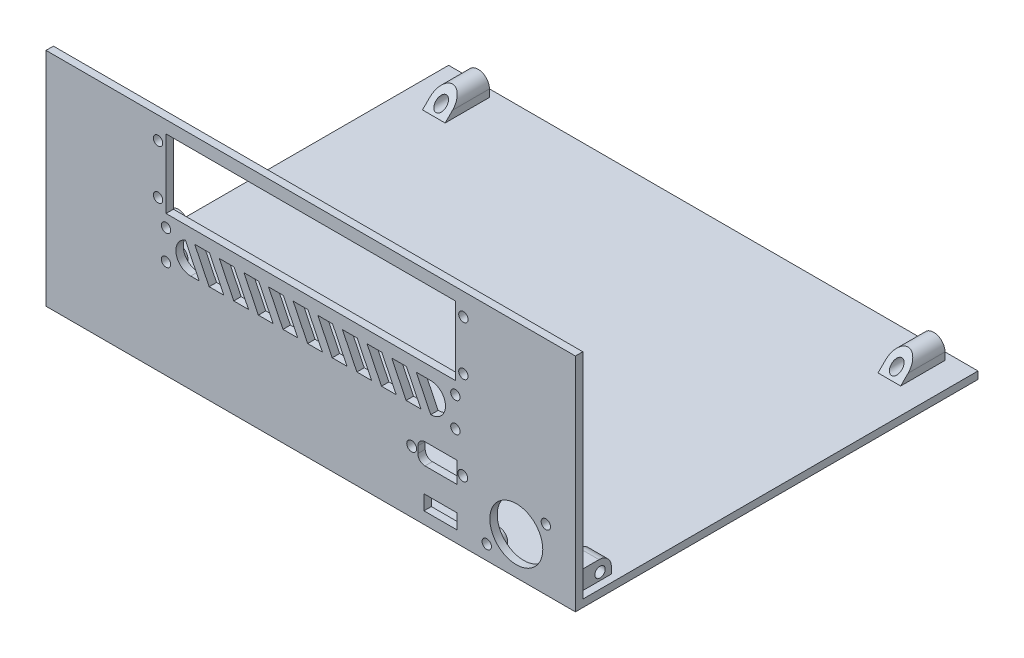
SolidWorks part; units mm, degrees
ref_plane "Płaszczyzna przednia" through (0, 0, 0) normal (0, 0, 1) x (1, 0, 0)
ref_plane "Płaszczyzna górna" through (0, 0, 0) normal (0, 1, 0) x (1, 0, 0)
ref_plane "Płaszczyzna prawa" through (0, 0, 0) normal (1, 0, 0) x (0, 0, -1)
sketch "Szkic1" plane through (0, 0, 0) normal (0, 0, 1) x (1, 0, 0)
  line L1 (0, 0) -> (215, 0)
  line L2 (0, 0) -> (0, 90)
  line L3 (0, 90) -> (215, 90)
  line L4 (215, 0) -> (215, 90)
  dimension "D1" = 215
  dimension "D2" = 90
extrude "Dodanie-wyciągnięcie1" add sketch "Szkic1" along normal blind 3
ref_plane "Płaszczyzna1" through (107.5, 0, 0) normal (1, 0, 0) x (0, 0, -1)
sketch "Szkic5" plane through (0, 0, 3) normal (0, 0, 1) x (1, 0, 0)
  line L0 (215, 90) -> (0, 90) construction
  line L1 (48.75, 85) -> (166.25, 85)
  line L2 (48.75, 85) -> (48.75, 57)
  line L3 (48.75, 57) -> (166.25, 57)
  line L4 (166.25, 85) -> (166.25, 57)
  line L5 (107.5, 90) -> (107.5, 105.9064) construction
  line L6 (48.75, 71) -> (107.5, 71) construction
  circle A0 centre (45.5, 81) radius 1.9
  circle A2 centre (45.5, 61) radius 1.9
  circle A3 centre (169.5, 61) radius 1.9
  circle A4 centre (169.5, 81) radius 1.9
  point P6 (107.5, 85)
  dimension "D6" = 3.8
  dimension "D4" = 20
  dimension "D1" = 5
  dimension "D2" = 28
  dimension "D3" = 117.5
  dimension "D5" = 62
extrude "Wytnij-wyciągnięcie2" cut sketch "Szkic5" against normal blind 35 contours A0 | A2 | A3 | A4 | L2 L3 L4 L1 region at (45.5, 81, 3) region at (45.5, 61, 3) region at (169.5, 61, 3) region at (169.5, 81, 3)
sketch "Szkic6" plane through (0, 0, 3) normal (0, 0, 1) x (1, 0, 0)
  line L1 (153.5, 10.8) -> (167, 10.8)
  line L2 (153.5, 10.8) -> (153.5, 4.8)
  line L3 (153.5, 4.8) -> (167, 4.8)
  line L4 (167, 10.8) -> (167, 4.8)
  line L10 (215, 0) -> (215, 90) construction
  line L11 (0, 0) -> (215, 0) construction
  line L13 (167, 20.8) -> (153.9, 20.8)
  line L14 (167, 20.8) -> (167, 29.3)
  line L15 (167, 29.3) -> (153.9, 29.3)
  line L16 (151, 23.7) -> (151, 26.4)
  circle A0 centre (191, 15.35) radius 10.75
  circle A1 centre (203, 24.85) radius 1.9
  circle A2 centre (179, 5.85) radius 1.9
  arc A3 (153.9, 20.8) -> (151, 23.7) centre (153.9, 23.7) cw
  arc A4 (153.9, 29.3) -> (151, 26.4) centre (153.9, 26.4) ccw
  circle A5 centre (148.5, 25.05) radius 2
  circle A6 centre (169.25, 25.05) radius 2
  point P16 (151, 20.8)
  dimension "D9" = 3.8
  dimension "D10" = 3.8
  dimension "D15" = 21.5
  dimension "D16" = 2.9
  dimension "D21" = 4
  dimension "D22" = 4
  dimension "D3" = 8.5
  dimension "D4" = 16
  dimension "D1" = 48
  dimension "D2" = 13.5
  dimension "D5" = 6
  dimension "D6" = 4.8
  dimension "D7" = 24
  dimension "D8" = 15.35
  dimension "D11" = 12
  dimension "D12" = 9.5
  dimension "D13" = 12
  dimension "D14" = 9.5
  dimension "D17" = 24
  dimension "D18" = 10
  dimension "D19" = 2.5
  dimension "D20" = 2.25
extrude "Wytnij-wyciągnięcie3" cut sketch "Szkic6" against normal through all
sketch "Szkic8" plane through (0, 0, 0) normal (0, 0, -1) x (-1, 0, 0)
  circle A0 centre (-179, 5.85) radius 3.5
  circle A1 centre (-203, 24.85) radius 3.5
  circle A2 centre (-203, 24.85) radius 2
  circle A3 centre (-179, 5.85) radius 2
  dimension "D1" = 7
  dimension "D2" = 7
  dimension "D3" = 4
  dimension "D4" = 4
extrude "Dodanie-wyciągnięcie4" add sketch "Szkic8" along normal blind 2
sketch "Szkic9" plane through (0, 0, 0) normal (0, 0, -1) x (-1, 0, 0)
  line L0 (-156.25, 46) -> (-58.75, 46) construction
  line L1 (-156.25, 52) -> (-58.75, 52)
  line L2 (-156.25, 40) -> (-58.75, 40)
  line L3 (-166.25, 57) -> (-48.75, 57) construction
  line L4 (-166.25, 57) -> (-166.25, 85) construction
  line L5 (-48.75, 57) -> (-48.75, 85) construction
  line L6 (-156.25, 40) -> (-150.385, 52)
  line L7 (-152.25, 40) -> (-146.385, 52)
  line L8 (-146.25, 40) -> (-140.385, 52)
  line L9 (-142.25, 40) -> (-136.385, 52)
  line L10 (-136.25, 40) -> (-130.385, 52)
  line L11 (-132.25, 40) -> (-126.385, 52)
  line L12 (-126.25, 40) -> (-120.385, 52)
  line L13 (-122.25, 40) -> (-116.385, 52)
  line L14 (-116.25, 40) -> (-110.385, 52)
  line L15 (-112.25, 40) -> (-106.385, 52)
  line L16 (-106.25, 40) -> (-100.385, 52)
  line L17 (-102.25, 40) -> (-96.385, 52)
  line L18 (-96.25, 40) -> (-90.385, 52)
  line L19 (-92.25, 40) -> (-86.385, 52)
  line L20 (-86.25, 40) -> (-80.385, 52)
  line L21 (-82.25, 40) -> (-76.385, 52)
  line L22 (-76.25, 40) -> (-70.385, 52)
  line L23 (-72.25, 40) -> (-66.385, 52)
  line L24 (-66.25, 40) -> (-60.385, 52)
  line L25 (-62.25, 40) -> (-56.583, 51.595)
  line L26 (-107.5, -6.1587) -> (-107.5, 71.4956) construction
  line L29 (-107.5, 46) -> (-179.9248, 46) construction
  arc A0 (-156.25, 52) -> (-156.25, 40) centre (-156.25, 46) ccw
  arc A1 (-58.75, 40) -> (-58.75, 52) centre (-58.75, 46) ccw
  circle A2 centre (-166.25, 52) radius 1.9
  circle A3 centre (-166.25, 40) radius 1.9
  circle A4 centre (-48.75, 40) radius 1.9
  circle A5 centre (-48.75, 52) radius 1.9
  point P2 (-107.5, 46)
  point P57 (0, 0)
  point P58 (-107.5, 52)
  point P68 (-106.25, -6.1587)
  dimension "D7" = 3.8
  dimension "D1" = 11
  dimension "D2" = 10
  dimension "D3" = 10
  dimension "D4" = 12
  dimension "D5" = 4
  dimension "D8" = 6
  dimension "D9" = 10
  dimension "D6" = 10
extrude "Wytnij-wyciągnięcie4" cut sketch "Szkic9" against normal blind 3 contours A2 | A3 | L1 A0 L6 | L2 L8 L1 L7 | L2 L10 L1 L9 | L2 L12 L1 L11 | L2 L14 L1 L13 | L2 L16 L1 L15 | L2 L18 L1 L17 | L2 L20 L1 L19 | L2 L22 L1 L21 | L2 L24 L1 L23 | L2 A1 L25 | A4 | A5 region at (157.0698, 46.7672, 0) region at (146.3175, 46, 0) region at (136.3175, 46, 0) region at (126.3175, 46, 0) region at (116.3175, 46, 0) region at (106.3175, 46, 0) region at (96.3175, 46, 0) region at (86.3175, 46, 0) region at (76.3175, 46, 0) region at (66.3175, 46, 0) region at (56.7806, 44.9252, 0) region at (166.25, 52, 0) region at (166.25, 40, 0) region at (48.75, 40, 0) region at (48.75, 52, 0)
sketch "Szkic10" plane through (0, 0, 0) normal (0, 0, -1) x (-1, 0, 0)
  circle A0 centre (-166.25, 40) radius 1.9
  circle A2 centre (-166.25, 52) radius 1.9
  circle A3 centre (-48.75, 52) radius 1.9
  circle A4 centre (-48.75, 40) radius 1.9
  circle A5 centre (-166.25, 52) radius 4
  circle A6 centre (-166.25, 40) radius 4
  circle A7 centre (-48.75, 40) radius 4
  circle A8 centre (-48.75, 52) radius 4
  dimension "D1" = 8
extrude "Dodanie-wyciągnięcie5" add sketch "Szkic10" along normal blind 2
ref_plane "Plane1" through (0, 0, 3) normal (1, 0, 0) x (0, 0, -1)
sketch "Sketch2" plane through (0, 0, 0) normal (0, -1, 0) x (1, 0, 0)
  line L1 (0, 3) -> (215, 3)
  line L2 (0, 3) -> (0, -160.5)
  line L3 (0, -160.5) -> (215, -160.5)
  line L4 (215, 3) -> (215, -160.5)
extrude "Boss-Extrude1" add sketch "Sketch2" against normal blind 3
sketch "Sketch3" plane through (0, 0, -157.5) normal (0, 0, 1) x (1, 0, 0)
  circle A0 centre (15, 6) radius 1.6
  circle A1 centre (107.5, 18) radius 1.6
  circle A2 centre (200, 6) radius 1.6
  circle A3 centre (15, 6) radius 1.6 construction
  circle A4 centre (107.5, 18) radius 1.6 construction
  circle A5 centre (200, 6) radius 1.6 construction
sketch "Sketch4" plane through (3, 0, 0) normal (1, 0, 0) x (0, 0, -1)
  circle A0 centre (10, 6) radius 1.6
  circle A1 centre (10, 6) radius 1.6 construction
sketch "Sketch6" plane through (215, 0, 0) normal (1, 0, 0) x (0, 0, -1)
  circle A0 centre (10, 6) radius 1.6
  circle A1 centre (10, 6) radius 1.6 construction
ref_plane "Plane2" through (0, 0, -157.5) normal (0, 0, 1) x (1, 0, 0)
sketch "Sketch7" plane through (0, 0, -157.5) normal (0, 0, 1) x (1, 0, 0)
  line L0 (19.6, 6) -> (19.6, 0)
  line L1 (19.6, 0) -> (10.4, 0)
  line L2 (10.4, 0) -> (10.4, 6)
  line L3 (204.6, 6) -> (204.6, 0)
  line L4 (204.6, 0) -> (195.4, 0)
  line L5 (195.4, 0) -> (195.4, 6)
  line L6 (0, 0) -> (215, 0) construction
  arc A0 (19.6, 6) -> (10.4, 6) centre (15, 6) ccw
  arc A1 (204.6, 6) -> (195.4, 6) centre (200, 6) ccw
  circle A2 centre (15, 6) radius 2.1
  circle A3 centre (200, 6) radius 2.1
  dimension "D1" = 4.2
  dimension "D2" = 2.5
  dimension "D3" = 4.2
  dimension "D4" = 2.5
extrude "Boss-Extrude2" add sketch "Sketch7" along normal blind 10
chamfer "Chamfer1" distance 8 angle 45 2 edges at (200, 3, -147.5) (15, 3, -147.5)
ref_plane "Plane3" through (3, 0, 0) normal (1, 0, 0) x (0, 0, -1)
sketch "Sketch9" plane through (3, 0, 0) normal (1, 0, 0) x (0, 0, -1)
  line L0 (-3, 0) -> (160.5, 0) construction
  line L1 (0, 10.6) -> (14.6, 10.6)
  line L3 (0, 0) -> (14.6, 0)
  line L4 (14.6, 10.6) -> (14.6, 0)
  line L5 (0, 3) -> (0, 90) construction
  line L6 (0, 0) -> (0, 10.6)
  circle A0 centre (10, 6) radius 2.1
  dimension "D1" = 4.2
  dimension "D2" = 4.6
  dimension "D3" = 4.6
extrude "Boss-Extrude3" add sketch "Sketch9" along normal blind 8
ref_plane "Plane5" through (107.5, 0, 0) normal (1, 0, 0) x (0, 0, -1)
fillet "Fillet2" radius 5 1 edges at (7, 10.6, -14.6)
mirror "Mirror1" about plane through (107.5, 0, 0) normal (1, 0, 0) of "Boss-Extrude3", "Fillet2"
